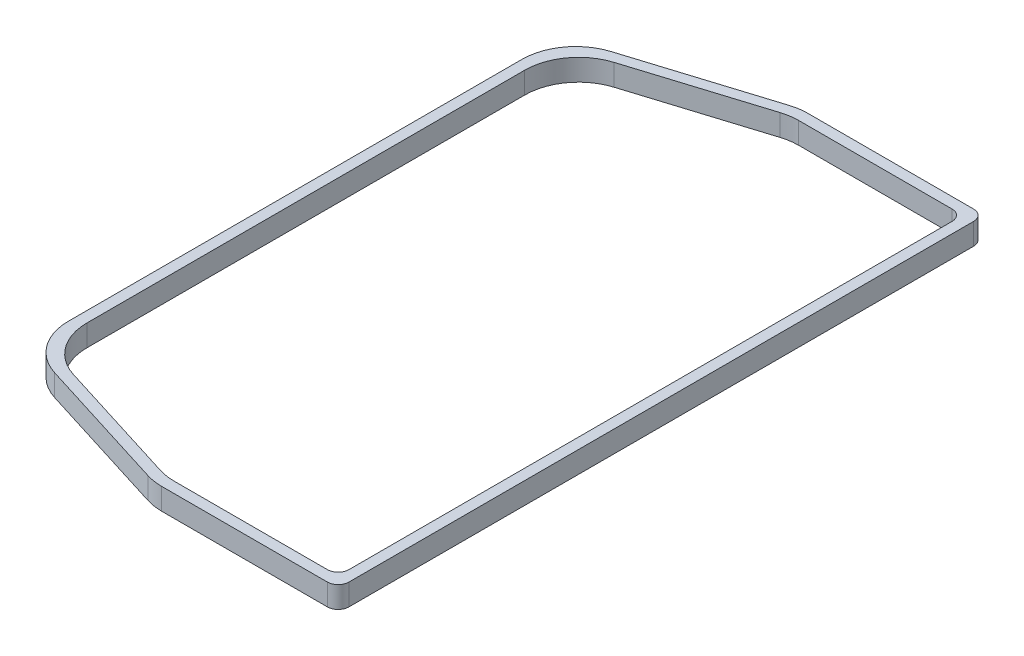
SolidWorks part; units mm, degrees
ref_plane "前视基准面" through (0, 0, 0) normal (0, 0, 1) x (1, 0, 0)
ref_plane "上视基准面" through (0, 0, 0) normal (0, 1, 0) x (1, 0, 0)
ref_plane "右视基准面" through (0, 0, 0) normal (1, 0, 0) x (0, 0, -1)
sketch "草图1" plane through (0, 0, 0) normal (0, 1, 0) x (1, 0, 0)
  line L0 (0, 0) -> (0, 29)
  line L1 (0, 29) -> (-16, 29)
  line L2 (-16, 29) -> (-32, 24)
  line L3 (-32, 24) -> (-32, 0)
  line L4 (0, 0) -> (-28.3305, 0) construction
  line L5 (1, 0) -> (1, 30)
  line L6 (1, 30) -> (-16.1526, 30)
  line L7 (-16.1526, 30) -> (-33, 24.7352)
  line L8 (-33, 24.7352) -> (-33, 0)
  line L9 (-33, 0) -> (-32, 0)
  line L10 (1, 0) -> (0, 0)
  dimension "D1" = 29
  dimension "D2" = 16
  dimension "D3" = 24
  dimension "D4" = 32
  dimension "D5" = 1
extrude "凸台-拉伸1" add sketch "草图1" along normal blind 2
fillet "圆角1" radius 5 4 edges at (-16, 1, -29) (-16.1526, 1, -30) (-33, 1, -24.7352) (-32, 1, -24)
fillet "圆角2" radius 1 2 edges at (1, 1, -30) (0, 1, -29)
mirror "镜向1" about plane through (0, 0, 0) normal (0, 0, 1) of "圆角1", "圆角2", "凸台-拉伸1"
